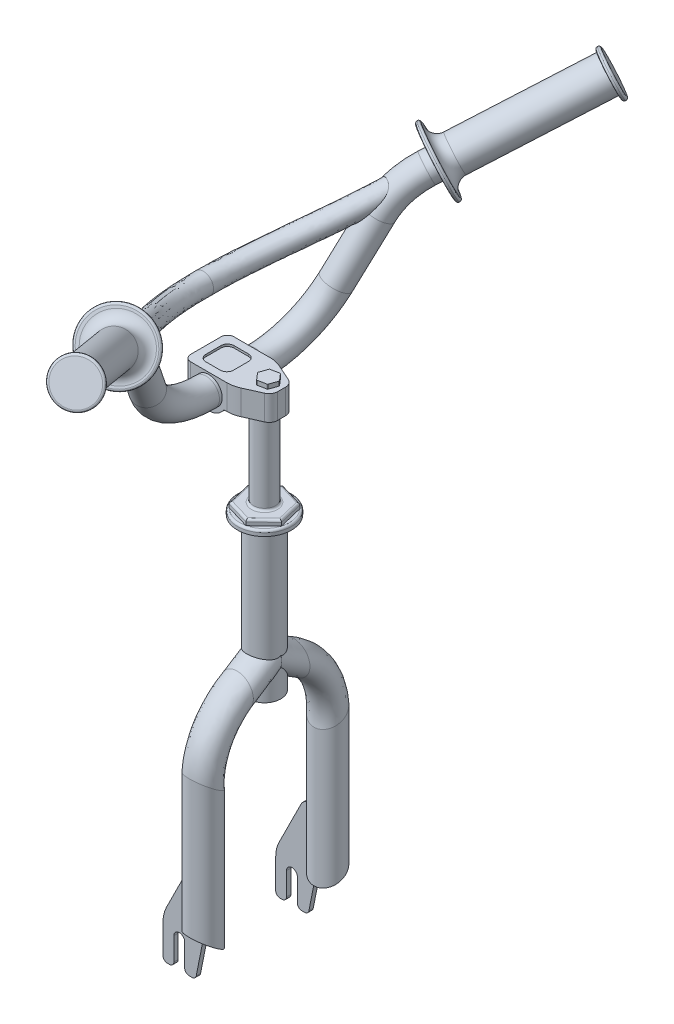
SolidWorks part; units mm, degrees
ref_plane "Front Plane" through (0, 0, 0) normal (0, 0, 1) x (1, 0, 0)
ref_plane "Top Plane" through (0, 0, 0) normal (0, 1, 0) x (1, 0, 0)
ref_plane "Right Plane" through (0, 0, 0) normal (1, 0, 0) x (0, 0, -1)
sketch "Sketch1" plane through (0, 0, 0) normal (0, 1, 0) x (1, 0, 0)
  line L0 (0, 0) -> (58.7362, 0) construction
  line L1 (0, 0) -> (-54.7895, 0) construction
  line L2 (4.4421, 20) -> (-29, 20)
  line L3 (-35, 14) -> (-35, -14)
  line L4 (-29, -20) -> (4.4421, -20)
  line L5 (15.0721, -17.7277) -> (30.2708, -10.9187)
  line L6 (35, -3.6179) -> (35, 3.6179)
  line L7 (30.2708, 10.9187) -> (15.0721, 17.7277)
  arc A0 (-35, -14) -> (-29, -20) centre (-29, -14) ccw
  arc A1 (-35, 14) -> (-29, 20) centre (-29, 14) cw
  arc A2 (15.0721, -17.7277) -> (4.4421, -20) centre (4.4421, 6) cw
  arc A3 (15.0721, 17.7277) -> (4.4421, 20) centre (4.4421, -6) ccw
  arc A4 (30.2708, -10.9187) -> (35, -3.6179) centre (27, -3.6179) ccw
  arc A5 (35, 3.6179) -> (30.2708, 10.9187) centre (27, 3.6179) ccw
  point P12 (-35, -20)
  point P15 (-35, 20)
  point P18 (10, -20)
  point P21 (10, 20)
  point P24 (35, -8.8)
  point P27 (35, 8.8)
  dimension "D6" = 6
  dimension "D7" = 26
  dimension "D8" = 8
  dimension "D1" = 70
  dimension "D2" = 40
  dimension "D3" = 17.6
  dimension "D4" = 45
  dimension "D5" = 35
extrude "Boss-Extrude1" add sketch "Sketch1" along normal mid plane 20
sketch "Sketch2" plane through (0, 0, 20) normal (0, 0, 1) x (1, 0, 0)
  line L0 (-35, 10) -> (-23.9, 10)
  line L1 (-29, 10) -> (4.4421, 10) construction
  line L2 (35, 10) -> (-0.7753, 10)
  line L3 (-35, 6) -> (-26.3265, 6)
  line L4 (35, 6) -> (1.6512, 6)
  line L5 (-35, 10) -> (-35, 6)
  line L6 (35, 10) -> (35, 6)
  arc A0 (-0.7753, 10) -> (-23.9, 10) centre (-12.3377, 14.75) cw
  arc A1 (1.6512, 6) -> (-26.3265, 6) centre (-12.3377, 14.75) cw
  dimension "D2" = 12.5
  dimension "D1" = 4.75
  dimension "D3" = 11.1
  dimension "D4" = 4
extrude "Cut-Extrude1" cut sketch "Sketch2" against normal through all flip side to cut
sketch "Sketch4" plane through (0, 6, 0) normal (0, -1, 0) x (1, 0, 0)
  line L0 (35, -3.6179) -> (35, 3.6179) construction
  circle A0 centre (19.18, 0) radius 10
  dimension "D1" = 15.82
extrude "Boss-Extrude2" add sketch "Sketch4" along normal blind 225
ref_plane "Plane1" through (20, 0, 0) normal (1, 0, 0) x (0, 0, -1)
sketch "Sketch6" plane through (20, 0, 0) normal (1, 0, 0) x (0, 0, -1)
  line L0 (0, -219) -> (0, -241.9386) construction
  line L1 (-10, -219) -> (10, -219) construction
  line L2 (0, -189) -> (-26.1206, -205.6947)
  line L3 (-57.5, -262.9916) -> (-57.5, -389.8697)
  arc A0 (-26.1206, -205.6947) -> (-57.5, -262.9916) centre (10.5, -262.9916) ccw
  dimension "D3" = 68
  dimension "D1" = 30
  dimension "D2" = 57.5
sketch "Sketch7" plane through (0, 0, 0) normal (0, 0, 1) x (1, 0, 0)
  circle A0 centre (20, -189) radius 15
  dimension "D1" = 30
sweep "Sweep1" add profiles "Sketch7" path "Sketch6"
mirror "Mirror1" about plane through (0, 0, 0) normal (0, 0, 1) of "Sweep1"
sketch "Sketch8" plane through (0, -219, 0) normal (0, -1, 0) x (1, 0, 0)
  circle A2 centre (19.18, 0) radius 15
extrude "Boss-Extrude3" add sketch "Sketch8" against normal blind 150
ref_plane "Plane2" through (0, 0, 50) normal (0, 0, 1) x (1, 0, 0)
sketch "Sketch9" plane through (0, 0, 50) normal (0, 0, 1) x (1, 0, 0)
  line L0 (20, -413) -> (20, -360.8018) construction
  line L3 (-20.5, -397.6811) -> (-20.5, -424.6197)
  line L4 (-16.5, -428.6197) -> (-14.5, -428.6197)
  line L5 (-10.5, -424.6197) -> (-10.5, -403.6197)
  line L7 (-0.5, -403.6197) -> (-0.5, -424.6197)
  line L8 (3.5, -428.6197) -> (6.2193, -428.6197)
  line L9 (10.142, -425.4024) -> (17, -391.0354)
  line L10 (17, -391.0354) -> (14.5, -389.8697)
  line L11 (14.5, -389.8697) -> (14.5, -338.6197)
  line L12 (5, -389.8697) -> (35, -389.8697) construction
  line L13 (-17.3502, -384.2996) -> (2.8412, -343.7853)
  arc A2 (-0.5, -403.6197) -> (-10.5, -403.6197) centre (-5.5, -403.6197) ccw
  arc A3 (2.8412, -343.7853) -> (14.5, -338.6197) centre (11.7913, -348.2458) cw
  arc A4 (-17.3502, -384.2996) -> (-20.5, -397.6811) centre (9.5, -397.6811) ccw
  arc A5 (6.2193, -428.6197) -> (10.142, -425.4024) centre (6.2193, -424.6197) ccw
  arc A6 (-0.5, -424.6197) -> (3.5, -428.6197) centre (3.5, -424.6197) ccw
  arc A7 (-14.5, -428.6197) -> (-10.5, -424.6197) centre (-14.5, -424.6197) ccw
  arc A8 (-20.5, -424.6197) -> (-16.5, -428.6197) centre (-16.5, -424.6197) ccw
  ellipse E0 centre (20, -389.8697) end of major axis (5, -389.8697) minor radius 8.0781 construction
  point P30 (-20.5, -390.6197)
  point P33 (9.5, -428.6197)
  point P38 (-0.5, -428.6197)
  point P41 (-10.5, -428.6197)
  point P44 (-20.5, -428.6197)
  dimension "D12" = 10
  dimension "D13" = 4
  dimension "D9" = 30
  dimension "D14" = 2.8412
  dimension "D15" = 6.2193
  dimension "D1" = 11
  dimension "D2" = 10
  dimension "D3" = 10
  dimension "D4" = 10
  dimension "D5" = 25
  dimension "D6" = 25
  dimension "D7" = 38
  dimension "D8" = 115
  dimension "D10" = 38.75
  dimension "D11" = 90
  dimension "D16" = 9.5
  dimension "D17" = 11.7913
extrude "Boss-Extrude4" add sketch "Sketch9" along normal blind 4 separate body
mirror "Mirror6" about plane through (0, 0, 0) normal (0, 0, 1) of bodies 107
sketch "Sketch10" plane through (0, 0, 0) normal (0, 0, 1) x (1, 0, 0)
  circle A0 centre (-12.3377, 14.75) radius 12.5
  arc A1 (-23.9, 10) -> (-0.7753, 10) centre (-12.3377, 14.75) ccw construction
  dimension "D1" = 25
sketch3d "3DSketch2"
  line L0 (-12.3377, 14.75, 0) -> (-12.3377, 14.75, 22.537)
  line L1 (-1.8444, 53.0949, 86.9128) -> (11.7238, 102.6763, 112.6608)
  line L2 (28.038, 131.9854, 140.9744) -> (91.1623, 186.75, 245.4093)
  arc A0 (28.038, 131.9854, 140.9744) -> (11.7238, 102.6763, 112.6608) centre (46.4186, 66.383, 164.2657) ccw
  arc A1 (-12.3377, 14.75, 22.537) -> (-1.8444, 53.0949, 86.9128) centre (6.6667, 84.1966, 22.537) ccw
  point P2 (17.1623, 122.55, 122.9813)
  point P3 (91.1623, 186.75, 245.4093)
  point P8 (17.1623, 122.55, 122.9813)
  point P9 (-14.3394, 63.0237, 202.7517)
  point P12 (-12.3377, 14.75, 67)
  point P13 (-62.7799, 103.201, 22.537)
  dimension "D8" = 72
  dimension "D1" = 67
  dimension "D2" = 29.5
  dimension "D3" = 107.8
  dimension "D4" = 125
  dimension "D5" = 103.5
  dimension "D6" = 172
  dimension "D7" = 156.8
sweep "Sweep2" add profiles "Sketch10" path "3DSketch2"
mirror "Mirror7" about plane through (0, 0, 0) normal (0, 0, 1) of bodies 109
sketch "Sketch18" plane through (0, 0, 0) normal (0, 0, 1) x (1, 0, 0)
  circle A0 centre (-37.3377, 77.75) radius 9.5
  arc A1 (-23.9, 10) -> (-0.7753, 10) centre (-12.3377, 14.75) ccw construction
  dimension "D2" = 19
  dimension "D1" = 63
  dimension "D3" = 25
sketch3d "3DSketch3"
  line L0 (-37.3377, 77.75, 43.9993) -> (-37.3377, 77.75, -55.6952) construction
  circle A0 centre (28.038, 131.9854, 140.9744) radius 12.5 construction
  spline S0 degree 3 poles (-37.3377, 77.75, 0) (-37.3377, 77.75, 62.3091) (6.254, 107.3262, 96.2409) (28.038, 131.9854, 140.9744) knots 0 0 0 0 1 1 1 1
  point P7 (33.9372, 137.1034, 150.7343)
sketch3d "3DSketch5" plane through (0, 0, 0) normal (0, 0, 1) x (1, 0, 0)
sweep "Sweep4" add profiles "Sketch18" path "3DSketch3"
mirror "Mirror9" about plane through (0, 0, 0) normal (0, 0, 1) of "Sweep4"
sketch "Sketch19" plane through (146.8197, 127.376, 242.9031) normal (0.4719, 0.4094, 0.7808) x (0.8816, -0.2192, -0.418)
  circle A0 centre (-63.1299, 51.4189) radius 15.85
  dimension "D1" = 31.7
extrude "Boss-Extrude6" add sketch "Sketch19" against normal blind 123
sketch "Sketch20" plane through (88.7712, 77.015, 146.8659) normal (-0.4719, -0.4094, -0.7808) x (-0.8816, 0.2192, 0.418)
  circle A0 centre (63.689, 51.3401) radius 30
  dimension "D1" = 60
extrude "Boss-Extrude7" add sketch "Sketch20" along normal blind 4
sketch "Sketch21" plane through (146.8197, 127.376, 242.9031) normal (0.4719, 0.4094, 0.7808) x (0.8816, -0.2192, -0.418)
  circle A0 centre (-62.5538, 50.6768) radius 20
extrude "Boss-Extrude9" add sketch "Sketch21" along normal blind 4
mirror "Mirror10" about plane through (0, 0, 0) normal (0, 0, 1) of "Boss-Extrude6", "Boss-Extrude7", "Boss-Extrude9"
fillet "Fillet3" radius 2 8 edges at (108.7865, 185.9665, 235.1674) (110.6743, 187.6043, 238.2906) (6.9466, 136.4418, 165.1609) (5.0589, 134.804, 162.0377) (6.9466, 136.4418, -165.1609) (5.0589, 134.804, -162.0377) (108.7865, 185.9665, -235.1674) (110.6743, 187.6043, -238.2906)
fillet "Fillet4" radius 10 2 edges at (46.6785, 136.389, -141.1731) (19.5492, 136.389, 157.571)
sketch "Sketch24" plane through (0, 10, 0) normal (0, 1, 0) x (1, 0, 0)
  line L4 (-29, -20) -> (-23.9, -20)
  line L5 (-23.9, -20) -> (-23.9, 20)
  line L6 (-23.9, 20) -> (-29, 20)
  line L7 (-35, 14) -> (-35, -14)
  line L8 (-29, -20) -> (-23.9, -20)
  line L9 (-23.9, -20) -> (-23.9, 20)
  line L10 (-23.9, 20) -> (-29, 20)
  line L11 (-35, 14) -> (-35, -14)
  line L14 (4.4421, 20) -> (-0.7753, 20)
  line L15 (-0.7753, 20) -> (-0.7753, -20)
  line L16 (-0.7753, -20) -> (4.4421, -20)
  line L17 (15.0721, -17.7277) -> (30.2708, -10.9187)
  line L18 (35, -3.6179) -> (35, 3.6179)
  line L19 (30.2708, 10.9187) -> (15.0721, 17.7277)
  line L20 (4.4421, 20) -> (-0.7753, 20)
  line L21 (-0.7753, 20) -> (-0.7753, -20)
  line L22 (-0.7753, -20) -> (4.4421, -20)
  line L23 (15.0721, -17.7277) -> (30.2708, -10.9187)
  line L24 (35, -3.6179) -> (35, 3.6179)
  line L25 (30.2708, 10.9187) -> (15.0721, 17.7277)
  arc A2 (-29, 20) -> (-35, 14) centre (-29, 14) ccw
  arc A3 (-35, -14) -> (-29, -20) centre (-29, -14) ccw
  arc A4 (-29, 20) -> (-35, 14) centre (-29, 14) ccw
  arc A5 (-35, -14) -> (-29, -20) centre (-29, -14) ccw
  arc A8 (4.4421, -20) -> (15.0721, -17.7277) centre (4.4421, 6) ccw
  arc A9 (30.2708, -10.9187) -> (35, -3.6179) centre (27, -3.6179) ccw
  arc A10 (35, 3.6179) -> (30.2708, 10.9187) centre (27, 3.6179) ccw
  arc A11 (15.0721, 17.7277) -> (4.4421, 20) centre (4.4421, -6) ccw
  arc A12 (4.4421, -20) -> (15.0721, -17.7277) centre (4.4421, 6) ccw
  arc A13 (30.2708, -10.9187) -> (35, -3.6179) centre (27, -3.6179) ccw
  arc A14 (35, 3.6179) -> (30.2708, 10.9187) centre (27, 3.6179) ccw
  arc A15 (15.0721, 17.7277) -> (4.4421, 20) centre (4.4421, -6) ccw
  dimension "D1" = 0
  dimension "D2" = 0
extrude "Boss-Extrude10" add sketch "Sketch24" along normal blind 4
sketch "Sketch25" plane through (0, 0, 0) normal (0, 0, 1) x (1, 0, 0)
  line L0 (-24.8151, 14) -> (-35, 14)
  line L1 (-35, 14) -> (-35, 29)
  line L2 (-35, 29) -> (35, 29)
  line L3 (35, 29) -> (35, 14)
  line L4 (35, 14) -> (0.1398, 14)
  circle A0 centre (-12.3377, 14.75) radius 12.5 construction
  arc A4 (0.1398, 14) -> (-24.8151, 14) centre (-12.3377, 14.75) ccw
  arc A5 (-24.8151, 14) -> (0.1398, 14) centre (-12.3377, 14.75) ccw construction
  point P3 (-24.8151, 14)
  point P5 (-12.3377, 14.75)
  dimension "D1" = 15
extrude "Boss-Extrude12" add sketch "Sketch25" along normal mid plane 40 contours L1 L2 L3 L4 A4 L0
sketch "Sketch41" plane through (0, 14, 0) normal (0, -1, 0) x (1, 0, 0)
  line L3 (15.0721, 17.7277) -> (30.2708, 10.9187)
  line L4 (35, 3.6179) -> (35, 20)
  line L5 (35, 20) -> (4.4421, 20)
  line L6 (15.0721, 17.7277) -> (30.2708, 10.9187)
  line L7 (35, 3.6179) -> (35, 20)
  line L8 (35, 20) -> (4.4421, 20)
  line L9 (30.2708, -10.9187) -> (15.0721, -17.7277)
  line L10 (4.4421, -20) -> (35, -20)
  line L11 (35, -20) -> (35, -3.6179)
  line L12 (30.2708, -10.9187) -> (15.0721, -17.7277)
  line L13 (4.4421, -20) -> (35, -20)
  line L14 (35, -20) -> (35, -3.6179)
  line L18 (4.4421, 20) -> (1.6512, 20)
  line L19 (1.6512, 20) -> (1.6512, -20)
  line L20 (1.6512, -20) -> (4.4421, -20)
  line L21 (15.0721, -17.7277) -> (30.2708, -10.9187)
  line L22 (35, -3.6179) -> (35, 3.6179)
  line L23 (30.2708, 10.9187) -> (15.0721, 17.7277)
  line L24 (4.4421, 20) -> (1.6512, 20)
  line L25 (1.6512, 20) -> (1.6512, -20)
  line L26 (1.6512, -20) -> (4.4421, -20)
  line L27 (15.0721, -17.7277) -> (30.2708, -10.9187)
  line L28 (35, -3.6179) -> (35, 3.6179)
  line L29 (30.2708, 10.9187) -> (15.0721, 17.7277)
  arc A2 (15.0721, 17.7277) -> (4.4421, 20) centre (4.4421, -6) ccw
  arc A3 (35, 3.6179) -> (30.2708, 10.9187) centre (27, 3.6179) ccw
  arc A4 (15.0721, 17.7277) -> (4.4421, 20) centre (4.4421, -6) ccw
  arc A5 (35, 3.6179) -> (30.2708, 10.9187) centre (27, 3.6179) ccw
  arc A6 (30.2708, -10.9187) -> (35, -3.6179) centre (27, -3.6179) ccw
  arc A7 (4.4421, -20) -> (15.0721, -17.7277) centre (4.4421, 6) ccw
  arc A8 (30.2708, -10.9187) -> (35, -3.6179) centre (27, -3.6179) ccw
  arc A9 (4.4421, -20) -> (15.0721, -17.7277) centre (4.4421, 6) ccw
  arc A12 (15.0721, 17.7277) -> (4.4421, 20) centre (4.4421, -6) ccw
  arc A13 (4.4421, -20) -> (15.0721, -17.7277) centre (4.4421, 6) ccw
  arc A14 (30.2708, -10.9187) -> (35, -3.6179) centre (27, -3.6179) ccw
  arc A15 (35, 3.6179) -> (30.2708, 10.9187) centre (27, 3.6179) ccw
  arc A16 (15.0721, 17.7277) -> (4.4421, 20) centre (4.4421, -6) ccw
  arc A17 (4.4421, -20) -> (15.0721, -17.7277) centre (4.4421, 6) ccw
  arc A18 (30.2708, -10.9187) -> (35, -3.6179) centre (27, -3.6179) ccw
  arc A19 (35, 3.6179) -> (30.2708, 10.9187) centre (27, 3.6179) ccw
  arc M31 (4.4421, 20) -> (15.0721, 17.7277) centre (4.4421, -6) cw
  line M32 (15.0721, 17.7277) -> (30.2708, 10.9187)
  arc M33 (30.2708, 10.9187) -> (35, 3.6179) centre (27, 3.6179) cw
  line M34 (35, 3.6179) -> (35, 20)
  line M35 (35, 20) -> (4.4421, 20)
  dimension "D1" = 0
  dimension "D2" = 0
  dimension "D3" = 0
extrude "Cut-Extrude7" cut sketch "Sketch41" against normal blind 40 contours M35 M31 M32 M33 M34 | A9 L13 L14 A8 L12 region at (26.6552, 14, 16.0563) region at (26.6552, 14, -16.0563)
fillet "Fillet7" radius 6 2 edges at (-35, 21.5, -20) (-35, 21.5, 20)
sketch "Sketch42" plane through (0, -69, 0) normal (0, 1, 0) x (1, 0, 0)
  line L1 (35.9183, 15.8979) -> (13.7674, 22.43)
  line L2 (13.7674, 22.43) -> (-2.9651, 6.5128)
  line L3 (-2.9651, 6.5128) -> (2.4534, -15.9366)
  line L4 (2.4534, -15.9366) -> (24.6044, -22.4687)
  line L5 (24.6044, -22.4687) -> (41.3368, -6.5514)
  line L6 (41.3368, -6.5514) -> (35.9183, 15.8979)
  circle A1 centre (19.1859, -0.0193) radius 20 construction
  dimension "D1" = 40
extrude "Boss-Extrude13" add sketch "Sketch42" against normal blind 5
sketch "Sketch43" plane through (0, -74, 0) normal (0, -1, 0) x (1, 0, 0)
  circle A0 centre (19.1815, -0.0152) radius 25
  dimension "D1" = 50
extrude "Boss-Extrude15" add sketch "Sketch43" along normal blind 5 contours A0
fillet "Fillet9" radius 2 8 edges at (32.9706, -69, 14.51) (13.5289, -69, 19.2026) (-0.2558, -69, 4.7119) (5.4011, -69, -14.4714) (24.8428, -69, -19.164) (38.6276, -69, -4.6733) (19.18, -69, -10) (19.1815, -74, -25.0152)
sketch "Sketch44" plane through (0, 29, 0) normal (0, 1, 0) x (1, 0, 0)
  circle A0 centre (23, 0) radius 6
  dimension "D1" = 12
  dimension "D2" = 23
extrude "Cut-Extrude8" cut sketch "Sketch44" against normal blind 20
sketch "Sketch45" plane through (0, 29, 0) normal (0, 1, 0) x (1, 0, 0)
  line L1 (-22, -13) -> (-8.5579, -13)
  line L2 (-28, 7) -> (-28, -7)
  line L3 (-8.5579, 13) -> (-22, 13)
  line L4 (-2.5579, 7) -> (-2.5579, -7)
  arc A0 (-22, -13) -> (-28, -7) centre (-22, -7) cw
  arc A1 (-8.5579, -13) -> (-2.5579, -7) centre (-8.5579, -7) ccw
  arc A2 (-8.5579, 13) -> (-2.5579, 7) centre (-8.5579, 7) cw
  arc A3 (-28, 7) -> (-22, 13) centre (-22, 7) cw
  dimension "D1" = 6
extrude "Cut-Extrude9" cut sketch "Sketch45" against normal blind 2 contours L3 A3 L2 A0 L1 A1 L4 A2
sketch "Sketch46" plane through (0, 29, 0) normal (0, 1, 0) x (1, 0, 0)
  line L1 (28.5, -6.5) -> (31.3498, 1.6541)
  line L2 (31.3498, 1.6541) -> (25.7131, 8.1993)
  line L3 (25.7131, 8.1993) -> (17.2265, 6.5902)
  line L4 (17.2265, 6.5902) -> (14.3766, -1.5639)
  line L5 (14.3766, -1.5639) -> (20.0134, -8.109)
  line L6 (20.0134, -8.109) -> (28.5, -6.5)
  circle A0 centre (22.8632, 0.0451) radius 7.4806 construction
extrude "Boss-Extrude16" add sketch "Sketch46" along normal blind 4
fillet "Fillet10" radius 0.5 6 edges at (20.0134, 31, 8.109) (14.3766, 31, 1.5639) (17.2265, 31, -6.5902) (25.7131, 31, -8.1993) (31.3498, 31, -1.6541) (28.5, 31, 6.5)
